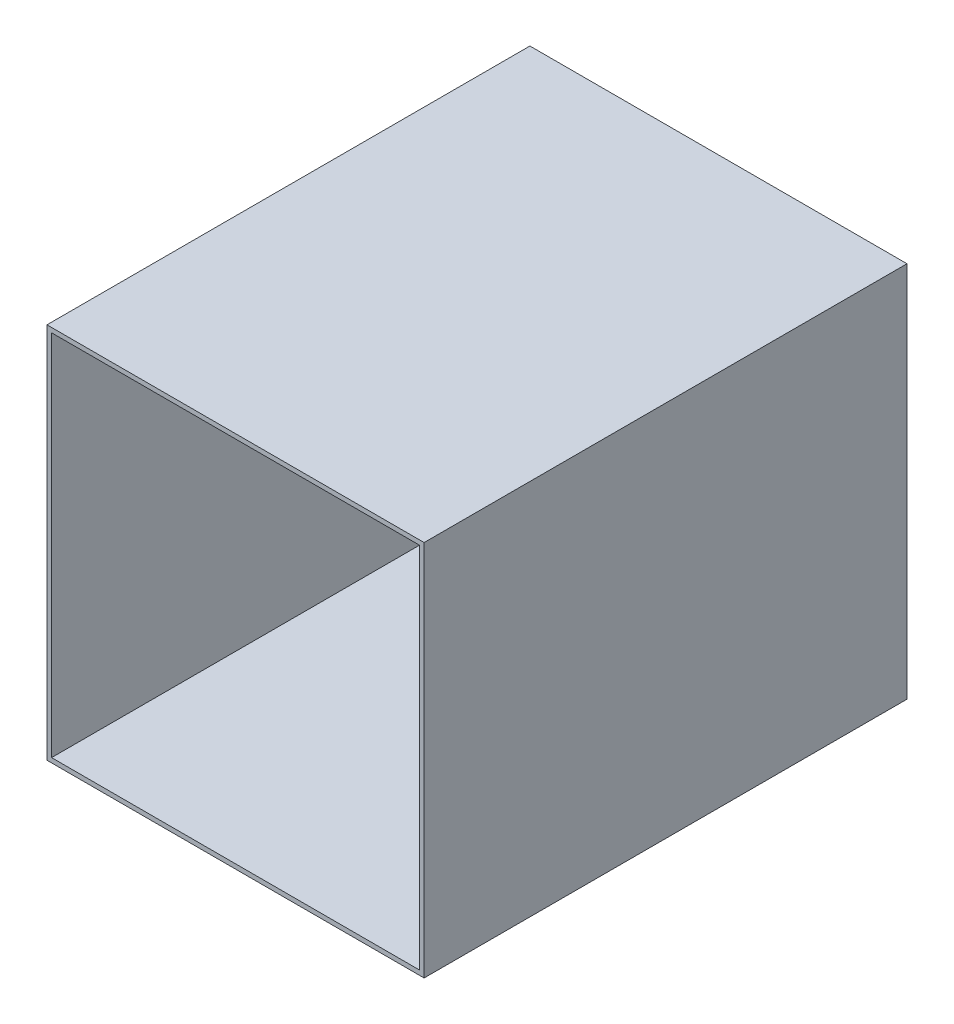
SolidWorks part; units mm, degrees
ref_plane "Front Plane" through (0, 0, 0) normal (0, 0, 1) x (1, 0, 0)
ref_plane "Top Plane" through (0, 0, 0) normal (0, 1, 0) x (1, 0, 0)
ref_plane "Right Plane" through (0, 0, 0) normal (1, 0, 0) x (0, 0, -1)
sketch "Sketch1" plane through (0, 0, 0) normal (0, 0, 1) x (1, 0, 0)
  line L0 (-3.175, 257.175) -> (257.175, 257.175)
  line L1 (0, 0) -> (254, 0)
  line L2 (0, 0) -> (0, 254)
  line L3 (0, 254) -> (254, 254)
  line L4 (254, 0) -> (254, 254)
  line L5 (257.175, -3.175) -> (257.175, 257.175)
  line L6 (-3.175, -3.175) -> (257.175, -3.175)
  line L7 (-3.175, -3.175) -> (-3.175, 257.175)
  dimension "D1" = 254
  dimension "D2" = 254
  dimension "D3" = 3.175
extrude "Boss-Extrude1" add sketch "Sketch1" along normal blind 330.2
extrude "Boss-Extrude2" add sketch "Sketch1<2>" against normal blind 3.175 contours L6 L5 L0 L7
sketch "Sketch1<2>" plane through (0, 0, 0) normal (0, 0, 1) x (1, 0, 0) same geometry as "Sketch1"
ref_axis "Axis1" through (254, 254, 165.1) along (-0.7071, -0.7071, 0)
ref_plane "Plane1" through (0, 0, 0) normal (-0.7071, 0.7071, 0) x (0.7071, 0.7071, 0)
